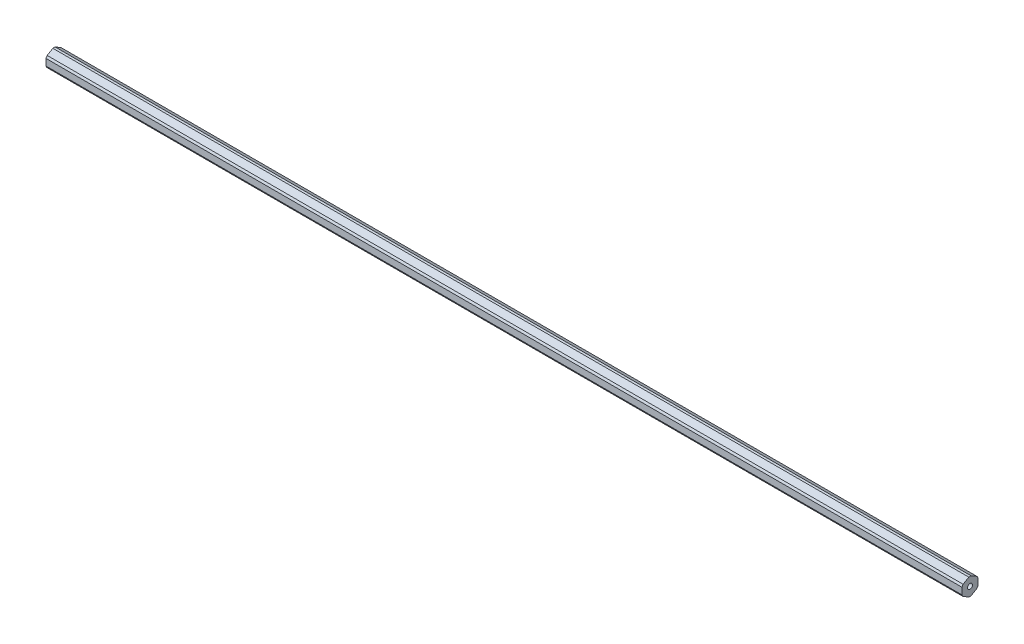
SolidWorks part; units mm, degrees
material "6061 Alloy"
ref_plane "Front Plane" through (0, 0, 0) normal (0, 0, 1) x (1, 0, 0)
ref_plane "Top Plane" through (0, 0, 0) normal (0, 1, 0) x (1, 0, 0)
ref_plane "Right Plane" through (0, 0, 0) normal (1, 0, 0) x (0, 0, -1)
ref_plane "Plane1" through (914.4, 0, 0) normal (1, 0, 0) x (0, 0, -1)
sketch "Sketch1" plane through (914.4, 0, 0) normal (1, 0, 0) x (0, 0, -1)
  line L0 (-5.4343, -4.1949) -> (-0.9157, -6.8037)
  line L1 (0.9157, -6.8037) -> (5.4343, -4.1949)
  line L2 (6.35, -2.6088) -> (6.35, 2.6088)
  line L3 (5.4343, 4.1949) -> (0.9157, 6.8037)
  line L4 (-0.9157, 6.8037) -> (-5.4343, 4.1949)
  line L5 (-6.35, 2.6088) -> (-6.35, -2.6088)
  circle A0 centre (0, 0) radius 1.9939
  arc A1 (-6.35, -2.6088) -> (-5.4343, -4.1949) centre (0, 0) ccw
  arc A2 (-0.9157, -6.8037) -> (0.9157, -6.8037) centre (0, 0) ccw
  arc A3 (5.4343, -4.1949) -> (6.35, -2.6088) centre (0, 0) ccw
  arc A4 (6.35, 2.6088) -> (5.4343, 4.1949) centre (0, 0) ccw
  arc A5 (0.9157, 6.8037) -> (-0.9157, 6.8037) centre (0, 0) ccw
  arc A6 (-5.4343, 4.1949) -> (-6.35, 2.6088) centre (0, 0) ccw
extrude "Boss-Extrude1" add sketch "Sketch1" against normal mid plane 723.9
equation "\"Hex Length\"= 28.5in"
equation "\"D1@Boss-Extrude1\"=\"Hex Length\""
